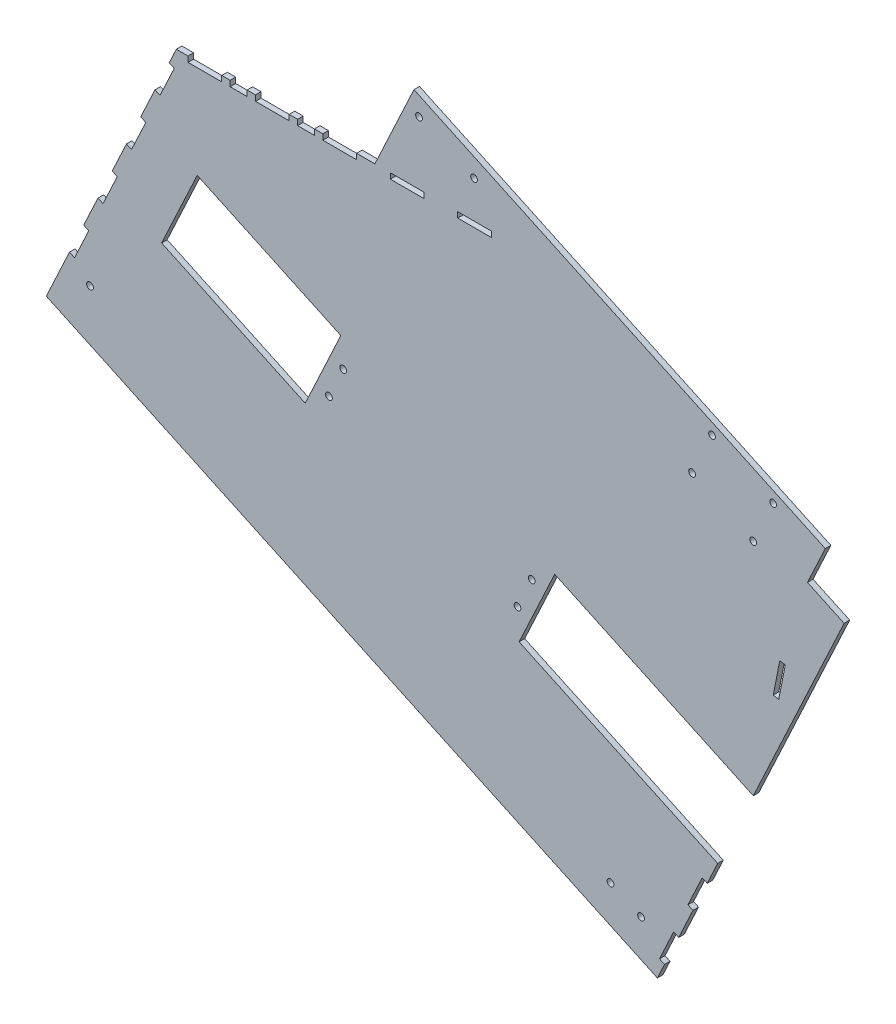
SolidWorks part; units mm, degrees
material "Balsa"
ref_plane "Front Plane" through (0, 0, 0) normal (0, 0, 1) x (1, 0, 0)
ref_plane "Top Plane" through (0, 0, 0) normal (0, 1, 0) x (1, 0, 0)
ref_plane "Right Plane" through (0, 0, 0) normal (1, 0, 0) x (0, 0, -1)
sketch "Sketch1" plane through (0, 0, 0) normal (0, 0, 1) x (1, 0, 0)
  line L0 (-255.2098, 12.6381) -> (-137.4275, 12.6381)
  line L1 (-137.4275, 12.6381) -> (-114.243, 62.3574)
  line L2 (-114.243, 62.3574) -> (129.7831, -51.4338)
  line L3 (129.7831, -51.4338) -> (119.2177, -74.0915)
  line L4 (119.2177, -74.0915) -> (140.969, -84.2344)
  line L5 (140.969, -84.2344) -> (30.1585, -321.8683)
  line L6 (30.1585, -321.8683) -> (-332.3646, -152.8209)
  line L7 (-332.3646, -152.8209) -> (-255.2098, 12.6381)
  line L9 (-332.3646, -152.8209) -> (-261.0998, 0.0069) construction
  line L10 (30.1585, -321.8683) -> (-332.3646, -152.8209) construction
  line L11 (140.969, -84.2344) -> (30.1585, -321.8683) construction
  line L12 (-189.2372, 97.3278) -> (129.7831, -51.4338) construction
  line L13 (119.2177, -74.0915) -> (140.969, -84.2344) construction
  line L14 (129.7831, -51.4338) -> (119.2177, -74.0915) construction
  circle A0 centre (87.0035, -69.0002) radius 2
  circle A1 centre (98.8369, -43.6236) radius 2
  circle A2 centre (62.5845, -26.7189) radius 2
  circle A3 centre (50.7512, -52.0955) radius 2
  circle A4 centre (2.3586, -286.8374) radius 2
  circle A5 centre (-306.4229, -134.5749) radius 2
  circle A6 centre (20.4847, -295.2897) radius 2
  circle A7 centre (2.3586, -286.8374) radius 2 construction
  circle A8 centre (20.4847, -295.2897) radius 2 construction
  point P0 (-137.4275, 12.6381)
  dimension "D1" = 4
  dimension "D2" = 4
  dimension "D3" = 4
  dimension "D4" = 4
  dimension "D7" = 4
  dimension "D5" = 27.5
  dimension "D6" = 15.8
extrude "Boss-Extrude1" add sketch "Sketch1" along normal up to surface (3.3 mm away)
sketch "Sketch2" plane through (0, 0, 0) normal (0, 0, -1) x (-1, 0, 0)
  line L0 (114.243, 62.3574) -> (137.4275, 12.6381) construction
  line L1 (-129.7831, -51.4338) -> (114.243, 62.3574) construction
  circle A0 centre (78.5916, 34.6991) radius 2
  circle A1 centre (111.2187, 49.9134) radius 2
  dimension "D1" = 4
  dimension "D2" = 4
  dimension "D3" = 8
  dimension "D4" = 36
  dimension "D5" = 10
  dimension "D6" = 10
extrude "Cut-Extrude1" cut sketch "Sketch2" against normal through all
sketch "Sketch5" plane through (0, 0, 3.3) normal (0, 0, 1) x (1, 0, 0)
  line L0 (65.9543, -245.104) -> (-51.8657, -190.1636)
  line L1 (140.969, -84.2344) -> (30.1585, -321.8683) construction
  line L2 (-51.8657, -190.1636) -> (-30.7348, -144.8482)
  line L3 (-30.7348, -144.8482) -> (87.0852, -199.7886)
  line L4 (87.0852, -199.7886) -> (65.9543, -245.104)
  line L5 (119.2177, -74.0915) -> (140.969, -84.2344) construction
  dimension "D1" = 130
  dimension "D2" = 127.5
  dimension "D3" = 50
extrude "Cut-Extrude2" cut sketch "Sketch5" against normal blind 10
sketch "Sketch6" plane through (0, 0, 3.3) normal (0, 0, 1) x (1, 0, 0)
  line L0 (-178.7488, -130.9971) -> (-157.6179, -85.6817)
  line L1 (-157.6179, -85.6817) -> (-242.8108, -45.9555)
  line L2 (-242.8108, -45.9555) -> (-263.9417, -91.2709)
  line L3 (-263.9417, -91.2709) -> (-178.7488, -130.9971)
  line L5 (87.0852, -199.7886) -> (-30.7348, -144.8482) construction
  line L6 (-51.8657, -190.1636) -> (65.9543, -245.104) construction
  line L7 (-332.3646, -152.8209) -> (-255.2098, 12.6381) construction
  line L8 (129.7831, -51.4338) -> (119.2177, -74.0915) construction
  dimension "D1" = 130
  dimension "D2" = 340
extrude "Cut-Extrude3" cut sketch "Sketch6" against normal blind 10
sketch "Sketch7" plane through (0, 0, 3.3) normal (0, 0, 1) x (1, 0, 0)
  circle A0 centre (-52.7985, -172.5711) radius 2
  circle A1 centre (-44.3462, -154.4449) radius 2
  circle A2 centre (-164.6725, -120.4034) radius 2
  circle A3 centre (-156.2202, -102.2772) radius 2
  circle A4 centre (-52.7985, -172.5711) radius 2 construction
  circle A5 centre (-44.3462, -154.4449) radius 2 construction
  circle A6 centre (-164.6725, -120.4034) radius 2 construction
  circle A7 centre (-156.2202, -102.2772) radius 2 construction
extrude "Cut-Extrude4" cut sketch "Sketch7" against normal blind 10
sketch "Sketch8" plane through (0, 0, 3.3) normal (0, 0, 1) x (1, 0, 0)
  line L0 (-255.2098, 12.6381) -> (-137.4275, 12.6381) construction
  line L1 (-248.2814, 12.6381) -> (-228.2814, 12.6381)
  line L2 (-248.2814, 12.6381) -> (-248.2814, 9.3381)
  line L3 (-248.2814, 9.3381) -> (-228.2814, 9.3381)
  line L4 (-228.2814, 12.6381) -> (-228.2814, 9.3381)
  line L5 (-248.2814, 12.6381) -> (-228.2814, 9.3381) construction
  line L6 (-248.2814, 9.3381) -> (-228.2814, 12.6381) construction
  line L7 (-248.2814, 9.3381) -> (-248.2814, 12.6381) construction
  line L8 (-208.2814, 12.6381) -> (-188.2814, 12.6381)
  line L9 (-208.2814, 12.6381) -> (-208.2814, 9.3381)
  line L10 (-208.2814, 9.3381) -> (-188.2814, 9.3381)
  line L11 (-188.2814, 12.6381) -> (-188.2814, 9.3381)
  line L12 (-208.2814, 12.6381) -> (-188.2814, 9.3381) construction
  line L13 (-208.2814, 9.3381) -> (-188.2814, 12.6381) construction
  line L14 (-168.2814, 12.6381) -> (-148.2814, 12.6381)
  line L15 (-168.2814, 12.6381) -> (-168.2814, 9.3381)
  line L16 (-168.2814, 9.3381) -> (-148.2814, 9.3381)
  line L17 (-148.2814, 12.6381) -> (-148.2814, 9.3381)
  line L18 (-168.2814, 12.6381) -> (-148.2814, 9.3381) construction
  line L19 (-168.2814, 9.3381) -> (-148.2814, 12.6381) construction
  line L20 (-128.2814, 12.6381) -> (-108.2814, 12.6381)
  line L21 (-128.2814, 12.6381) -> (-128.2814, 9.3381)
  line L22 (-128.2814, 9.3381) -> (-108.2814, 9.3381)
  line L23 (-108.2814, 12.6381) -> (-108.2814, 9.3381)
  line L24 (-128.2814, 12.6381) -> (-108.2814, 9.3381) construction
  line L25 (-128.2814, 9.3381) -> (-108.2814, 12.6381) construction
  line L26 (-88.2814, 12.6381) -> (-68.2814, 12.6381)
  line L27 (-88.2814, 12.6381) -> (-88.2814, 9.3381)
  line L28 (-88.2814, 9.3381) -> (-68.2814, 9.3381)
  line L29 (-68.2814, 12.6381) -> (-68.2814, 9.3381)
  line L30 (-88.2814, 12.6381) -> (-68.2814, 9.3381) construction
  line L31 (-88.2814, 9.3381) -> (-68.2814, 12.6381) construction
  point P4 (-238.2814, 10.9881)
  point P14 (-198.2814, 10.9881)
  point P19 (-158.2814, 10.9881)
  point P24 (-118.2814, 10.9881)
  point P30 (-78.2814, 10.9881)
  dimension "D1" = 20
  dimension "D2" = 3.3
  dimension "D3" = 5
extrude "Cut-Extrude5" cut sketch "Sketch8" against normal blind 10
sketch "Sketch9" plane through (0, 0, 3.3) normal (0, 0, 1) x (1, 0, 0)
  line L0 (-259.4359, 3.575) -> (-256.4451, 2.1804)
  line L1 (-332.3646, -152.8209) -> (-255.2098, 12.6381) construction
  line L2 (-256.4451, 2.1804) -> (-264.8975, -15.9458)
  line L3 (-264.8975, -15.9458) -> (-267.8883, -14.5511)
  line L4 (-267.8883, -14.5511) -> (-259.4359, 3.575)
  line L5 (-276.3407, -32.6773) -> (-273.3499, -34.0719)
  line L6 (-273.3499, -34.0719) -> (-281.8022, -52.1981)
  line L7 (-281.8022, -52.1981) -> (-284.793, -50.8035)
  line L8 (-284.793, -50.8035) -> (-276.3407, -32.6773)
  line L9 (-293.2454, -68.9296) -> (-290.2546, -70.3242)
  line L10 (-290.2546, -70.3242) -> (-298.707, -88.4504)
  line L11 (-298.707, -88.4504) -> (-301.6978, -87.0558)
  line L12 (-301.6978, -87.0558) -> (-293.2454, -68.9296)
  line L13 (-310.1501, -105.1819) -> (-307.1593, -106.5766)
  line L14 (-307.1593, -106.5766) -> (-315.6117, -124.7027)
  line L15 (-315.6117, -124.7027) -> (-318.6025, -123.3081)
  line L16 (-318.6025, -123.3081) -> (-310.1501, -105.1819)
  dimension "D1" = 3.3
  dimension "D2" = 20
  dimension "D3" = 10
  dimension "D4" = 4
extrude "Cut-Extrude6" cut sketch "Sketch9" against normal blind 10
sketch "Sketch10" plane through (0, 0, 3.3) normal (0, 0, 1) x (1, 0, 0)
  line L0 (-255.2098, 12.6381) -> (-137.4275, 12.6381) construction
  line L1 (-173.2814, 12.6381) -> (-183.2814, 12.6381)
  line L2 (-173.2814, 12.6381) -> (-173.2814, 9.3381)
  line L3 (-173.2814, 9.3381) -> (-183.2814, 9.3381)
  line L4 (-183.2814, 12.6381) -> (-183.2814, 9.3381)
  line L5 (-173.2814, 12.6381) -> (-183.2814, 9.3381) construction
  line L6 (-173.2814, 9.3381) -> (-183.2814, 12.6381) construction
  line L7 (-188.2814, 9.3381) -> (-188.2814, 12.6381) construction
  line L8 (-213.2814, 12.6381) -> (-223.2814, 12.6381)
  line L9 (-213.2814, 12.6381) -> (-213.2814, 9.3381)
  line L10 (-213.2814, 9.3381) -> (-223.2814, 9.3381)
  line L11 (-223.2814, 12.6381) -> (-223.2814, 9.3381)
  line L12 (-213.2814, 12.6381) -> (-223.2814, 9.3381) construction
  line L13 (-213.2814, 9.3381) -> (-223.2814, 12.6381) construction
  point P4 (-178.2814, 10.9881)
  point P15 (-218.2814, 10.9881)
  dimension "D1" = 10
  dimension "D2" = 3.3
  dimension "D3" = 5
  dimension "D4" = 2
extrude "Cut-Extrude7" cut sketch "Sketch10" against normal blind 3.3
sketch "Sketch11" plane through (0, 0, 3.3) normal (0, 0, 1) x (1, 0, 0)
  line L0 (34.3847, -312.8052) -> (31.3939, -311.4105)
  line L1 (65.9543, -245.104) -> (30.1585, -321.8683) construction
  line L2 (31.3939, -311.4105) -> (39.8463, -293.2844)
  line L3 (39.8463, -293.2844) -> (42.8371, -294.679)
  line L4 (42.8371, -294.679) -> (34.3847, -312.8052)
  line L5 (30.1585, -321.8683) -> (-332.3646, -152.8209) construction
  line L6 (51.2895, -276.5529) -> (48.2986, -275.1582)
  line L7 (48.2986, -275.1582) -> (56.751, -257.0321)
  line L8 (56.751, -257.0321) -> (59.7418, -258.4267)
  line L9 (59.7418, -258.4267) -> (51.2895, -276.5529)
  dimension "D1" = 3.3
  dimension "D2" = 20
  dimension "D3" = 10
  dimension "D4" = 2
extrude "Cut-Extrude8" cut sketch "Sketch11" against normal blind 3.3
sketch "Sketch12" plane through (0, 0, 0) normal (0, 0, -1) x (-1, 0, 0)
  line L0 (-102.7901, -122.4718) -> (-98.923, -142.0944)
  line L1 (-102.7901, -122.4718) -> (-106.0279, -123.1099)
  line L2 (-98.923, -142.0944) -> (-102.1607, -142.7325)
  line L3 (-106.0279, -123.1099) -> (-102.1607, -142.7325)
  line L4 (-119.2177, -74.0915) -> (-140.969, -84.2344) construction
  line L6 (-93.7982, -185.1655) -> (-102.1607, -142.7325) construction
  dimension "D1" = 50
  dimension "D2" = 3.3
  dimension "D3" = 20
extrude "Cut-Extrude9" cut sketch "Sketch12" against normal blind 3.3
